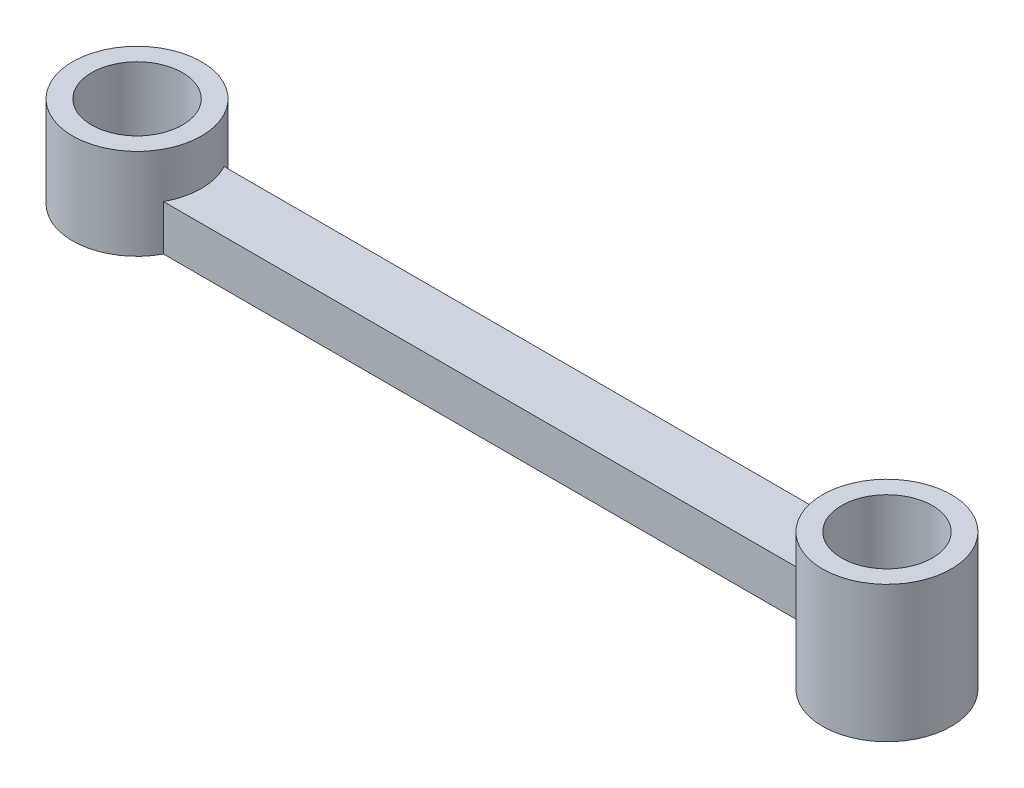
SolidWorks part; units mm, degrees
ref_plane "Front Plane" through (0, 0, 0) normal (0, 0, 1) x (1, 0, 0)
ref_plane "Top Plane" through (0, 0, 0) normal (0, 1, 0) x (1, 0, 0)
ref_plane "Right Plane" through (0, 0, 0) normal (1, 0, 0) x (0, 0, -1)
sketch "Sketch2" plane through (0, 0, 0) normal (0, 1, 0) x (1, 0, 0)
  line L0 (0, 13.5649) -> (0, -12.5178) construction
  line L1 (21, 2) -> (-21, 2)
  line L2 (21, -2) -> (-21, -2)
  line L3 (-3.0991, 0) -> (4.143, 0) construction
  circle A0 centre (-24.75, 0) radius 3
  circle A1 centre (-24.75, 0) radius 4.25
  circle A2 centre (24.75, 0) radius 4.25
  circle A3 centre (24.75, 0) radius 3
  point P14 (0, -2)
  point P15 (0, 2)
  dimension "D1" = 49.5
  dimension "D2" = 6
  dimension "D3" = 8.5
  dimension "D4" = 4
extrude "Boss-Extrude1" add sketch "Sketch2" along normal blind 3 contours L2 A2 L1 A1 region at (0, 0, 0)
extrude "Boss-Extrude2" add sketch "Sketch2<3>" along normal blind 6 contours A1 A0 region at (-20.7435, 0, -1.0016)
sketch "Sketch2<3>" plane through (0, 0, 0) normal (0, 1, 0) x (1, 0, 0) same geometry as "Sketch2"
extrude "Boss-Extrude3" add sketch "Sketch2<4>" along normal blind 6 and the other way blind 3 contours A2 A3 region at (25.7516, 0, -4.0065)
sketch "Sketch2<4>" plane through (0, 0, 0) normal (0, 1, 0) x (1, 0, 0) same geometry as "Sketch2"
